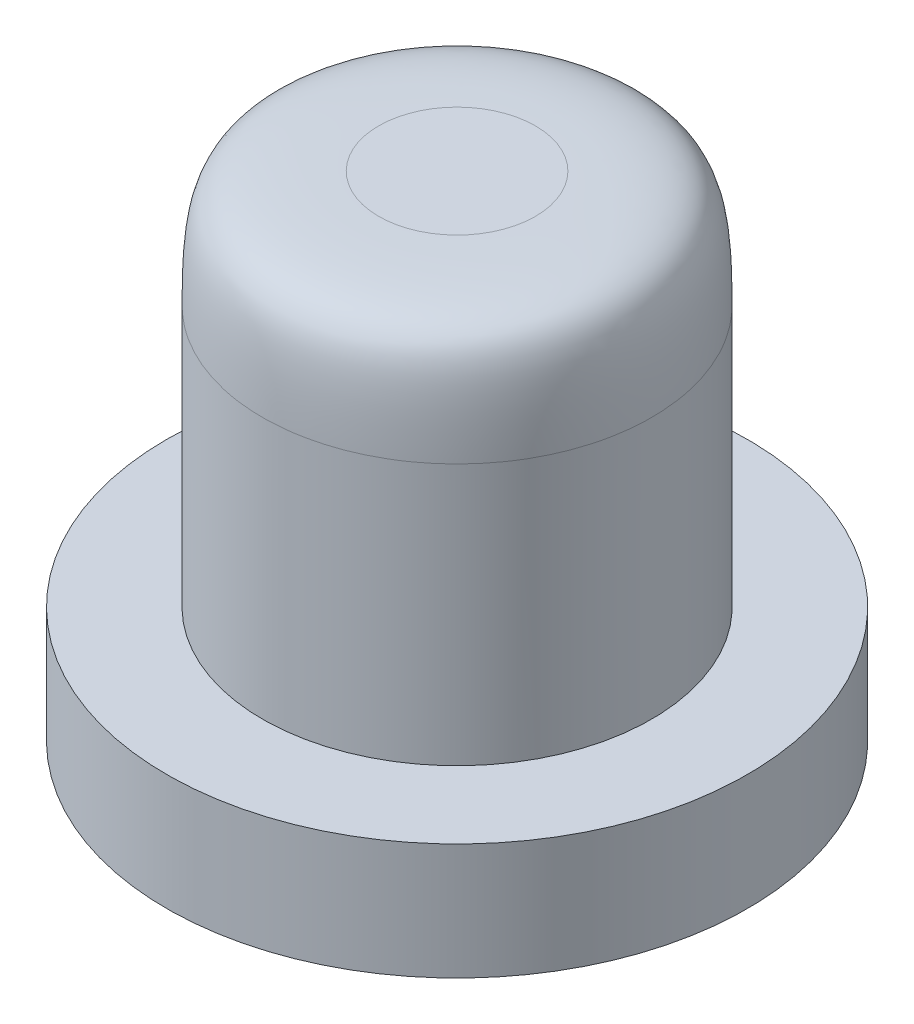
SolidWorks part; units mm, degrees
ref_plane "Plan de face" through (0, 0, 0) normal (0, 0, 1) x (1, 0, 0)
ref_plane "Plan de dessus" through (0, 0, 0) normal (0, 1, 0) x (1, 0, 0)
ref_plane "Plan de droite" through (0, 0, 0) normal (1, 0, 0) x (0, 0, -1)
sketch "Esquisse1" plane through (0, 0, 0) normal (0, 0, 1) x (1, 0, 0)
  line L0 (0, 0) -> (5, 0)
  line L1 (5, 0) -> (5, 2)
  line L2 (5, 2) -> (3.35, 2)
  line L3 (3.35, 2) -> (3.35, 8.5)
  line L4 (3.35, 8.5) -> (0, 8.5)
  line L5 (0, 8.5) -> (0, 0)
  dimension "D1" = 6.5
  dimension "D2" = 2
  dimension "D3" = 3.35
  dimension "D4" = 5
revolve "Révolution1" add sketch "Esquisse1" angle 360 about L5
fillet "Congé1" radius 2 1 edges at (-3.35, 8.5, 0) conic rho 0.7
